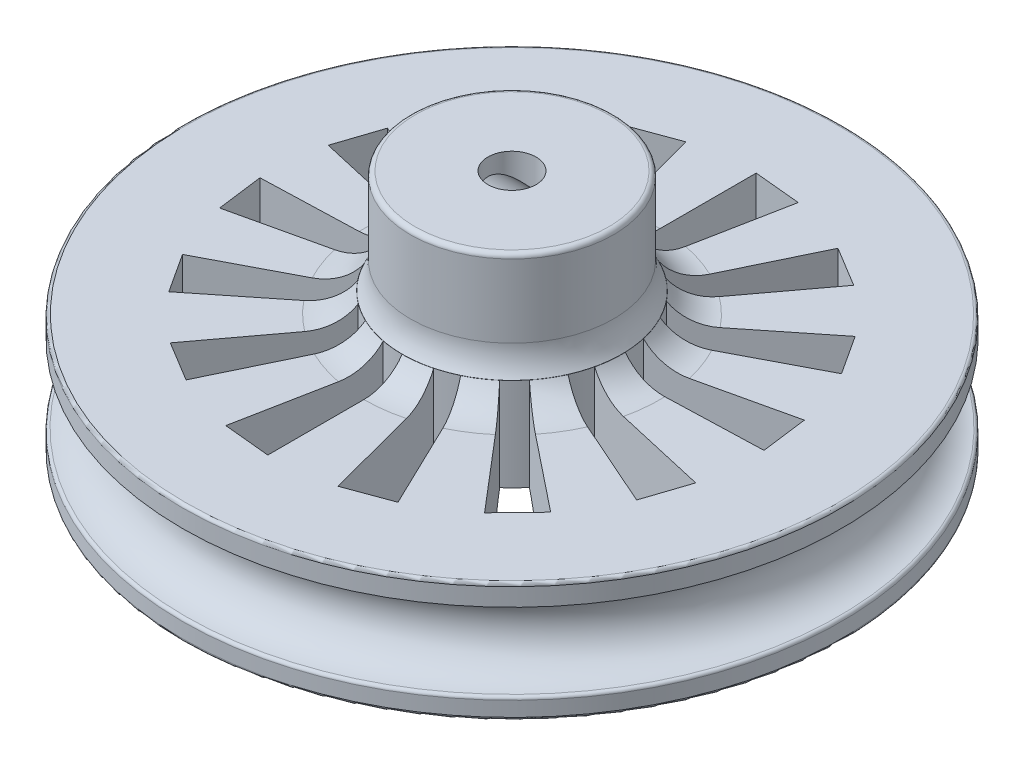
SolidWorks part; units mm, degrees
ref_plane "Front Plane" through (0, 0, 0) normal (0, 0, 1) x (1, 0, 0)
ref_plane "Top Plane" through (0, 0, 0) normal (0, 1, 0) x (1, 0, 0)
ref_plane "Right Plane" through (0, 0, 0) normal (1, 0, 0) x (0, 0, -1)
sketch "Sketch1" plane through (0, 0, 0) normal (0, 1, 0) x (1, 0, 0)
  circle A0 centre (0, 0) radius 19.6
  dimension "D1" = 39.2
extrude "Boss-Extrude1" add sketch "Sketch1" along normal blind 7.7
sketch "Sketch2" plane through (0, 0, 0) normal (1, 0, 0) x (0, 0, -1)
  line L0 (19.6, 7.7) -> (-19.6, 7.7) construction
  line L1 (-19.6, 7.7) -> (-19.6, 0) construction
  line L2 (0, 11.9347) -> (0, -4.2297) construction
  circle A0 centre (-19.6, 3.85) radius 2.9813
  dimension "D1" = 3.85
  dimension "D2" = 0
revolve "Cut-Revolve1" cut sketch "Sketch2" angle 360 about L2
sketch "Sketch4" plane through (0, 7.7, 0) normal (0, 1, 0) x (1, 0, 0)
  circle A0 centre (0, 0) radius 6.55
  dimension "D1" = 13.1
extrude "Boss-Extrude3" add sketch "Sketch4" along normal blind 6
sketch "Sketch7" plane through (0, 13.7, 0) normal (0, 1, 0) x (1, 0, 0)
  circle A0 centre (0, 0) radius 1.55
  dimension "D1" = 3.1
extrude "Cut-Extrude3" cut sketch "Sketch7" against normal blind 10
sketch "Sketch10" plane through (0, 0, 0) normal (0, -1, 0) x (-1, 0, 0)
  circle A0 centre (0, 0) radius 21.25
  dimension "D1" = 42.5
extrude "Boss-Extrude4" add sketch "Sketch10" against normal up to surface (7.7 mm away) up to face at (0, 7.7, 6.55)
sketch "Sketch11" plane through (0, 0, 0) normal (1, 0, 0) x (0, 0, -1)
  line L0 (21.25, 0) -> (21.25, 7.7) construction
  line L2 (0, 0) -> (0, 23.1716) construction
  circle A0 centre (21.25, 3.85) radius 2.5
  dimension "D1" = 5
revolve "Cut-Revolve2" cut sketch "Sketch11" angle 360 about L2
fillet "Fillet6" radius 0.2 3 edges at (0, 7.7, 21.25) (0, 0, -21.25) (0, 1.35, 21.25)
sketch "Sketch12" plane through (0, 7.7, 0) normal (0, 1, 0) x (1, 0, 0)
  circle A0 centre (0, 0) radius 1.55
extrude "Cut-Extrude6" cut sketch "Sketch12" against normal blind 6.5
sketch "Sketch13" plane through (0, 13.7, 0) normal (0, 1, 0) x (1, 0, 0)
  circle A0 centre (0, 0) radius 6.55
  circle A1 centre (0, 0) radius 1.55
extrude "Boss-Extrude5" add sketch "Sketch13" along normal blind 2
sketch "Sketch8" plane through (0, 0, 0) normal (1, 0, 0) x (0, 0, -1)
  line L0 (6.55, 7.7) -> (-6.55, 7.7) construction
  circle A0 centre (0, 12.7) radius 1.9
  dimension "D1" = 3.8
  dimension "D2" = 5
  dimension "D3" = 5
extrude "Cut-Extrude4" cut sketch "Sketch8" against normal blind 10
fillet "Fillet7" radius 3 1 edges at (0, 7.7, 6.55)
fillet "Fillet8" radius 0.3 1 edges at (0, 15.7, 6.55)
sketch "Sketch14" plane through (0, 0, 0) normal (0, -1, 0) x (1, 0, 0)
  circle A0 centre (0, 0) radius 10
  dimension "D1" = 20
extrude "Cut-Extrude10" cut sketch "Sketch14" against normal blind 3
fillet "Fillet14" radius 7 1 edges at (0, 0, -10)
fillet "Fillet15" radius 7 1 edges at (0, 3, -10)
sketch "Sketch16" plane through (0, 3, 0) normal (0, -1, 0) x (1, 0, 0)
  line L0 (0, 3.5) -> (0, 15.7446)
  line L1 (0, 15.7446) -> (-3, 15.4561)
  line L2 (-3, 15.4561) -> (-0.6669, 3.4359)
  circle A0 centre (0, 0) radius 15.7446 construction
  circle A1 centre (0, 0) radius 3.5
  circle M4 centre (0, 0) radius 7.0843
  dimension "D2" = 7
  dimension "D1" = 3
extrude "Cut-Extrude11" cut sketch "Sketch16" against normal blind 6 and the other way blind 12 contours L1 L2 L0 M4 | A1 L0 L2 M4
sketch "Sketch17" plane through (0, 3, 0) normal (0, -1, 0) x (-1, 0, 0)
  circle A0 centre (0, 0) radius 7.0843
extrude "Boss-Extrude6" add sketch "Sketch17" against normal up to surface (6 mm away) up to face at (-0.5051, 9, 5.2527)
pattern_circular "CirPattern4" count 14 over 360 about axis through (0, 0, 0) along (0, 1, 0) of "Cut-Extrude11"
sketch "Sketch18" plane through (0, 3, 0) normal (0, -1, 0) x (-1, 0, 0)
  circle A0 centre (0, 0) radius 7.0843
extrude "Boss-Extrude7" add sketch "Sketch18" against normal blind 6
sketch "Sketch19" plane through (0, 9, 0) normal (0, 1, 0) x (1, 0, 0)
  circle A0 centre (0, 0) radius 1.55
extrude "Cut-Extrude12" cut sketch "Sketch19" against normal through all
